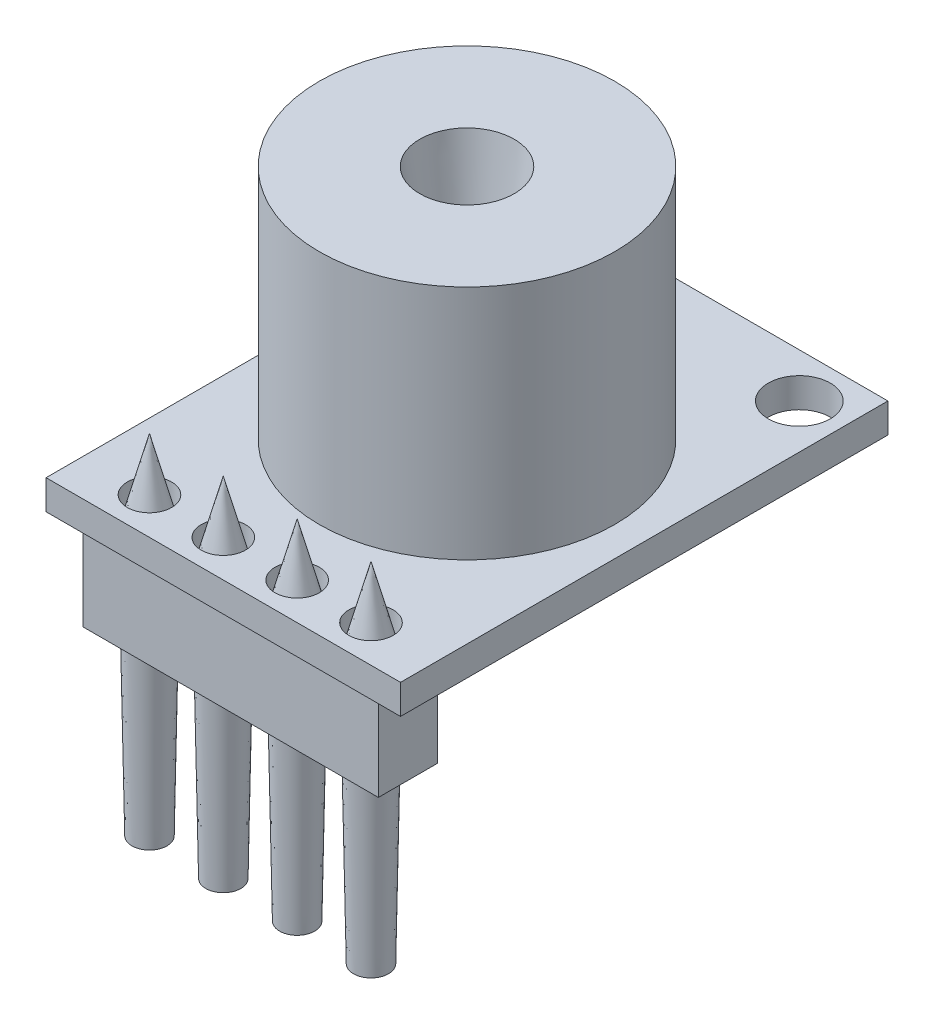
SolidWorks part; units mm, degrees
ref_plane "Piano frontale" through (0, 0, 0) normal (0, 0, 1) x (1, 0, 0)
ref_plane "Piano superiore" through (0, 0, 0) normal (0, 1, 0) x (1, 0, 0)
ref_plane "Piano destro" through (0, 0, 0) normal (1, 0, 0) x (0, 0, -1)
sketch "Schizzo1" plane through (0, 0, 0) normal (0, 1, 0) x (1, 0, 0)
  line L0 (-3.75, -7) -> (3.75, -7) construction
  line L1 (-6, 8.25) -> (6, 8.25)
  line L2 (-6, 8.25) -> (-6, -8.25)
  line L3 (-6, -8.25) -> (6, -8.25)
  line L4 (6, 8.25) -> (6, -8.25)
  line L5 (-6, 8.25) -> (6, -8.25) construction
  line L6 (-6, -8.25) -> (6, 8.25) construction
  circle A4 centre (-3.75, -7) radius 0.75
  circle A5 centre (-1.25, -7) radius 0.75
  circle A6 centre (1.25, -7) radius 0.75
  circle A7 centre (3.75, -7) radius 0.75
  circle A8 centre (4.5, 6.75) radius 1.05
  circle A9 centre (-4.5, 6.75) radius 1.05
  circle A10 centre (0, 0) radius 5
  circle A11 centre (0, 0) radius 1.599
  point P0 (0, 0)
  point P17 (0, 0)
  point P20 (0, -7)
  dimension "D3" = 2.1
  dimension "D5" = 1.5
  dimension "D9" = 4
  dimension "D6" = 1.5
  dimension "D1" = 16.5
  dimension "D2" = 12
  dimension "D4" = 1.5
  dimension "D10" = 7
extrude "Estrusione-Estrusione1" add sketch "Schizzo1" along normal blind 1 contours L4 L1 L2 L3 A10 A9 A8 A7 A6 A5 A4 | A10 A11 | A11
extrude "Estrusione-Estrusione2" add sketch "Schizzo1<3>" along normal blind 8 from surface separate body contours A10 starting at face at (-4.5, 1, -5.7)
sketch "Schizzo1<3>" plane through (0, 0, 0) normal (0, 1, 0) x (1, 0, 0) same geometry as "Schizzo1"
extrude "Estrusione-Estrusione3" add sketch "Schizzo1<4>" along normal blind 3 draft 15 separate body contours A4 | A5 | A6 | A7
sketch "Schizzo1<4>" plane through (0, 0, 0) normal (0, 1, 0) x (1, 0, 0) same geometry as "Schizzo1"
sketch "Schizzo3" plane through (0, 0, 0) normal (0, 1, 0) x (1, 0, 0)
  line L1 (-5, -6) -> (5, -6)
  line L2 (-5, -6) -> (-5, -8)
  line L3 (-5, -8) -> (5, -8)
  line L4 (5, -6) -> (5, -8)
  line L5 (-5, -6) -> (5, -8) construction
  line L6 (-5, -8) -> (5, -6) construction
  point P0 (0, -7)
  point P5 (0, 0)
  point P7 (0, 0)
  point P8 (0, 0)
  point P9 (0, 0)
  dimension "D1" = 10
  dimension "D2" = 2
  dimension "D3" = 7
extrude "Estrusione-Estrusione4" add sketch "Schizzo3" against normal blind 3 separate body
extrude "Estrusione-Estrusione5" add sketch "Schizzo1<5>" against normal blind 9 draft 1 separate body contours A4 | A5 | A6 | A7
sketch "Schizzo1<5>" plane through (0, 0, 0) normal (0, 1, 0) x (1, 0, 0) same geometry as "Schizzo1"
extrude "Taglio-Estrusione1" cut sketch "Schizzo1<6>" against normal blind 4 draft 8 from surface contours A11 starting at face at (0, 9, 5)
sketch "Schizzo1<6>" plane through (0, 0, 0) normal (0, 1, 0) x (1, 0, 0) same geometry as "Schizzo1"
